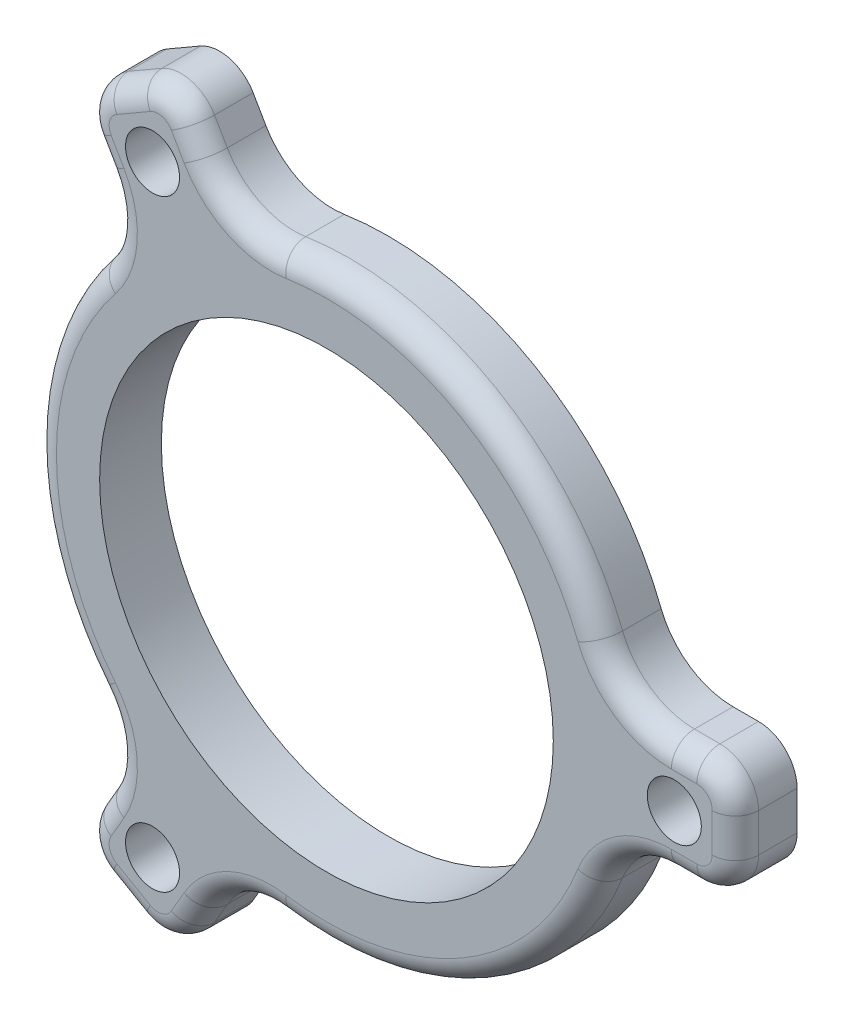
SolidWorks part; units mm, degrees
ref_plane "Front Plane" through (0, 0, 0) normal (0, 0, 1) x (1, 0, 0)
ref_plane "Top Plane" through (0, 0, 0) normal (0, 1, 0) x (1, 0, 0)
ref_plane "Right Plane" through (0, 0, 0) normal (1, 0, 0) x (0, 0, -1)
sketch "Sketch1" plane through (0, 0, 0) normal (0, 0, 1) x (1, 0, 0)
  line L11 (-34.3502, 16.25) -> (-29.8653, 16.25)
  line L12 (-29.8653, -16.25) -> (-34.3502, -16.25)
  line L13 (-28.8433, -34.958) -> (-30.4952, -37.8192)
  line L14 (-28.6651, -44.6493) -> (-24.3349, -47.1493)
  line L15 (-17.5048, -45.3192) -> (-15.8529, -42.458)
  line L16 (44.6962, -7.5) -> (48, -7.5)
  line L17 (53, -2.5) -> (53, 2.5)
  line L18 (48, 7.5) -> (44.6962, 7.5)
  line L19 (-15.8529, 42.458) -> (-17.5048, 45.3192)
  line L20 (-24.3349, 47.1493) -> (-28.6651, 44.6493)
  line L21 (-30.4952, 37.8192) -> (-28.8433, 34.958)
  line L24 (-28.8433, -34.958) -> (-30.4952, -37.8192)
  line L25 (-28.6651, -44.6493) -> (-24.3349, -47.1493)
  line L26 (-17.5048, -45.3192) -> (-15.8529, -42.458)
  line L27 (44.6962, -7.5) -> (48, -7.5)
  line L28 (53, -2.5) -> (53, 2.5)
  line L29 (48, 7.5) -> (44.6962, 7.5)
  line L30 (-15.8529, 42.458) -> (-17.5048, 45.3192)
  line L31 (-24.3349, 47.1493) -> (-28.6651, 44.6493)
  line L32 (-30.4952, 37.8192) -> (-28.8433, 34.958)
  circle A0 centre (45.0848, 0) radius 2.217 construction
  circle A1 centre (-22.5424, -39.0445) radius 2.217 construction
  circle A2 centre (-22.5424, 39.0445) radius 2.217 construction
  circle A3 centre (45.0848, 0) radius 2.217 construction
  circle A4 centre (-22.5424, -39.0445) radius 2.217 construction
  circle A5 centre (-22.5424, 39.0445) radius 2.217 construction
  circle A6 centre (0, 0) radius 29.4 construction
  circle A7 centre (0, 0) radius 29.4
  arc A11 (-29.8653, -16.25) -> (-29.8653, 16.25) centre (0, 0) ccw
  arc A12 (-34.3502, -16.25) -> (-29.6903, -23.7168) centre (0, 0) ccw
  arc A13 (-30.4952, -37.8192) -> (-28.6651, -44.6493) centre (-26.1651, -40.3192) ccw
  arc A14 (-24.3349, -47.1493) -> (-17.5048, -45.3192) centre (-21.8349, -42.8192) ccw
  arc A15 (-28.8433, -34.958) -> (-29.6903, -23.7168) centre (-37.5035, -29.958) ccw
  arc A16 (48, -7.5) -> (53, -2.5) centre (48, -2.5) ccw
  arc A17 (53, 2.5) -> (48, 7.5) centre (48, 2.5) ccw
  arc A18 (-28.8433, -34.958) -> (-29.6903, -23.7168) centre (-37.5035, -29.958) ccw
  arc A19 (-17.5048, 45.3192) -> (-24.3349, 47.1493) centre (-21.8349, 42.8192) ccw
  arc A20 (-28.6651, 44.6493) -> (-30.4952, 37.8192) centre (-26.1651, 40.3192) ccw
  arc A21 (-29.6903, 23.7168) -> (-34.3502, 16.25) centre (0, 0) ccw
  arc A23 (-34.3502, 16.25) -> (-29.6903, -23.7168) centre (0, 0) ccw
  arc A24 (-30.4952, -37.8192) -> (-28.6651, -44.6493) centre (-26.1651, -40.3192) ccw
  arc A25 (-24.3349, -47.1493) -> (-17.5048, -45.3192) centre (-21.8349, -42.8192) ccw
  arc A27 (48, -7.5) -> (53, -2.5) centre (48, -2.5) ccw
  arc A28 (53, 2.5) -> (48, 7.5) centre (48, 2.5) ccw
  arc A30 (-17.5048, 45.3192) -> (-24.3349, 47.1493) centre (-21.8349, 42.8192) ccw
  arc A31 (-28.6651, 44.6493) -> (-30.4952, 37.8192) centre (-26.1651, 40.3192) ccw
  arc A32 (-29.6903, 23.7168) -> (-34.3502, 16.25) centre (0, 0) ccw
  circle A53 centre (45.0848, 0) radius 3.5
  circle A54 centre (-22.5424, -39.0445) radius 3.5
  circle A55 centre (-22.5424, 39.0445) radius 3.5
  arc A67 (-5.6942, -37.5709) -> (-15.8529, -42.458) centre (-7.1927, -47.458) ccw
  arc A68 (-5.6942, -37.5709) -> (-15.8529, -42.458) centre (-7.1927, -47.458) ccw
  arc A69 (-5.6942, -37.5709) -> (35.3845, -13.8542) centre (0, 0) ccw
  arc A70 (-5.6942, -37.5709) -> (35.3845, -13.8542) centre (0, 0) ccw
  arc A71 (44.6962, -7.5) -> (35.3845, -13.8542) centre (44.6962, -17.5) ccw
  arc A72 (44.6962, -7.5) -> (35.3845, -13.8542) centre (44.6962, -17.5) ccw
  arc A73 (35.3845, 13.8542) -> (44.6962, 7.5) centre (44.6962, 17.5) ccw
  arc A74 (35.3845, 13.8542) -> (44.6962, 7.5) centre (44.6962, 17.5) ccw
  arc A75 (35.3845, 13.8542) -> (-5.6942, 37.5709) centre (0, 0) ccw
  arc A76 (35.3845, 13.8542) -> (-5.6942, 37.5709) centre (0, 0) ccw
  arc A77 (-15.8529, 42.458) -> (-5.6942, 37.5709) centre (-7.1927, 47.458) ccw
  arc A78 (-15.8529, 42.458) -> (-5.6942, 37.5709) centre (-7.1927, 47.458) ccw
  arc A79 (-29.6903, 23.7168) -> (-28.8433, 34.958) centre (-37.5035, 29.958) ccw
  arc A80 (-29.6903, 23.7168) -> (-28.8433, 34.958) centre (-37.5035, 29.958) ccw
  dimension "D2" = 7
  dimension "D3" = 7
  dimension "D4" = 7
  dimension "D1" = 0
extrude "Boss-Extrude1" add sketch "Sketch1" along normal blind 8
fillet "Fillet1" radius 3 24 edges at (-29.6692, -36.3886, 8) (-16.6789, -43.8886, 8) (-20.5408, -47.6488, 8) (-26.5, -45.8993, 8) (46.3481, 7.5, 8) (51.5355, 6.0355, 8) (53, 0, 8) (51.5355, -6.0355, 8) (-16.6789, 43.8886, 8) (-20.5408, 47.6488, 8) (-26.5, 45.8993, 8) (-30.9947, 41.6133, 8) (-30.9947, -41.6133, 8) (46.3481, -7.5, 8) (-29.6692, 36.3886, 8) (-38, 0, 8) (-27.5318, 29.2067, 8) (-11.5278, 38.4466, 8) (19, 32.909, 8) (39.0596, 9.2399, 8) (39.0596, -9.2399, 8) (19, -32.909, 8) (-11.5278, -38.4466, 8) (-27.5318, -29.2067, 8)
equation "\"D3@Sketch1\"=\"D2@Sketch1\""
equation "\"D4@Sketch1\"=\"D2@Sketch1\""
